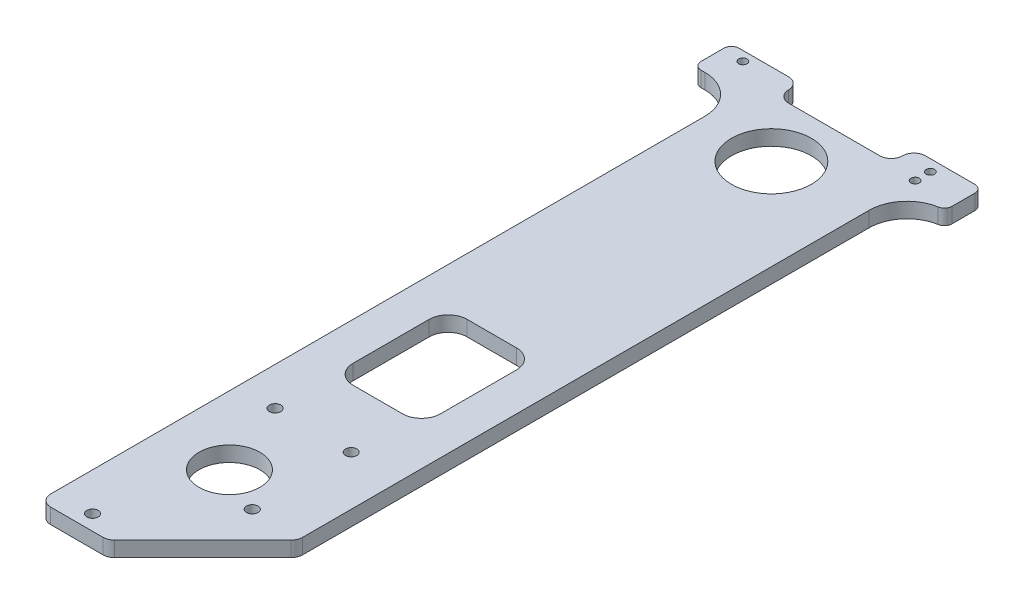
SolidWorks part; units mm, degrees
material "Thornel Mat VMA"
ref_plane "前视基准面" through (0, 0, 0) normal (0, 0, 1) x (1, 0, 0)
ref_plane "上视基准面" through (0, 0, 0) normal (0, 1, 0) x (1, 0, 0)
ref_plane "右视基准面" through (0, 0, 0) normal (1, 0, 0) x (0, 0, -1)
other "Configuration Table"
sketch "草图1" plane through (0, 0, 0) normal (0, 1, 0) x (1, 0, 0)
  line L0 (0, 0) -> (70.3815, 0) construction
  line L1 (-33, -97.5) -> (33, -97.5)
  line L2 (-33, -97.5) -> (-33, 97.5)
  line L3 (-33, 97.5) -> (33, 97.5)
  line L4 (33, -97.5) -> (33, 97.5)
  line L5 (-33, -97.5) -> (33, 97.5) construction
  line L6 (-33, 97.5) -> (33, -97.5) construction
  line L7 (0, -45.5) -> (63.9677, -45.5) construction
  line L8 (0, 0) -> (0, -67.9018) construction
  line L9 (0, 0) -> (0, 59.2148) construction
  line L14 (-20, -97.5) -> (-20, 87.5)
  line L15 (-20, 87.5) -> (-33, 87.5)
  line L16 (0, 92.5) -> (68.8821, 92.5) construction
  line L17 (-1.5, 44.6746) -> (-1.5, 61.6414) construction
  line L19 (-31, 88) -> (31, 88) construction
  line L20 (-31, 88) -> (-31, 97) construction
  line L21 (-31, 97) -> (31, 97) construction
  line L22 (31, 88) -> (31, 97) construction
  line L23 (-31, 88) -> (31, 97) construction
  line L24 (-31, 97) -> (31, 88) construction
  line L29 (23, -97.5243) -> (23, 87.5)
  line L30 (23, 87.5) -> (33, 87.5)
  line L37 (-10, -45.5) -> (-10, -112.6313) construction
  line L49 (10, -45.5) -> (10, -85.1506) construction
  line L50 (10, 0) -> (13, 0)
  line L55 (-10, -30) -> (10, -30)
  line L56 (-10, -30) -> (-10, 0)
  line L57 (-10, 0) -> (10, 0)
  line L58 (10, -30) -> (10, 0)
  line L59 (-10, -30) -> (10, 0) construction
  line L60 (-10, 0) -> (10, -30) construction
  line L61 (13, 0) -> (13, -30)
  line L62 (13, -30) -> (10, -30)
  line L63 (-1, 80.0182) -> (-1, 48.3003) construction
  line L66 (1.5, 44.6746) -> (1.5, 61.6414) construction
  line L68 (-33, 17.5) -> (-20, 17.5)
  line L69 (33, 17.5) -> (23, 17.5)
  circle A0 centre (10, -45.5) radius 1.5
  circle A1 centre (-10, -45.5) radius 1.5
  circle A2 centre (22.3, 94.5) radius 1.1
  circle A3 centre (22.3, 90.5) radius 1.1
  circle A4 centre (-27.5, 95) radius 1.1
  circle A6 centre (-10, -93.5) radius 1.5
  circle A7 centre (10, -71.5) radius 1.5
  circle A8 centre (-2, -65.5) radius 8
  circle A9 centre (-1, 76) radius 10.5
  point P0 (0, 0)
  point P34 (0, -15)
  dimension "D4" = 3
  dimension "D5" = 20
  dimension "D10" = 2.2
  dimension "D11" = 4
  dimension "D14" = 8.7
  dimension "D15" = 2.2
  dimension "D16" = 2
  dimension "D17" = 3.5
  dimension "D21" = 30
  dimension "D18" = 3
  dimension "D20" = 3
  dimension "D23" = 48
  dimension "D24" = 26
  dimension "D27" = 16
  dimension "D28" = 2
  dimension "D29" = 20
  dimension "D30" = 1
  dimension "D31" = 21
  dimension "D32" = 76
  dimension "D1" = 66
  dimension "D2" = 195
  dimension "D3" = 52
  dimension "D6" = 185
  dimension "D7" = 13
  dimension "D8" = 138
  dimension "D9" = 1.5
  dimension "D12" = 62
  dimension "D13" = 9
  dimension "D19" = 20
  dimension "D22" = 15
  dimension "D25" = 10
  dimension "D26" = 3
  dimension "D33" = 70
extrude "凸台-拉伸1" add sketch "草图1" along normal blind 4 contours L29 L30 L4 L3 L2 L15 L14 L1 A9 A8 A7 A6 A4 A1 A0 L61 L62 L55 L56 L57 L50 A2 A3 region at (1.5782, 0, -2.6188)
sketch "草图3" plane through (0, 4, 0) normal (0, 1, 0) x (1, 0, 0)
  line L0 (0, 0) -> (0, 63.5643) construction
  line L1 (-15, 97.5) -> (-15, 91.5)
  line L2 (-33, 97.5) -> (33, 97.5) construction
  line L3 (-15, 91.5) -> (15, 91.5)
  line L4 (-15, 97.5) -> (15, 97.5)
  line L5 (15, 97.5) -> (15, 91.5)
  point P10 (0, 97.5)
  point P11 (0, 91.5)
  dimension "D1" = 6
  dimension "D2" = 30
extrude "切除-拉伸1" cut sketch "草图3" against normal blind 5
fillet "圆角4" radius 3 4 edges at (15, 2, -97.5) (15, 2, -91.5) (-15, 2, -91.5) (-15, 2, -97.5)
chamfer "倒角1" distance 25 angle 45 1 edges at (23, 2, 97.5)
fillet "圆角8" radius 5 4 edges at (-10, 2, 30) (-10, 2, 0) (13, 2, 30) (13, 2, 0)
sketch "草图5" plane through (0, 4, 0) normal (0, 1, 0) x (1, 0, 0)
  line L0 (-33, -57.5) -> (-20, -57.5)
  line L1 (-33, 87.5) -> (-33, 97.5) construction
  line L2 (-20, -57.5) -> (-20, -97.5)
  line L4 (-20, -97.5) -> (-33, -97.5)
  line L5 (-33, -97.5) -> (-33, -57.5)
  line L6 (-20, -97.5) -> (-2, -97.5) construction
  dimension "D1" = 40
  dimension "D2" = 13
fillet "圆角12" radius 2 4 edges at (-33, 2, -97.5) (-33, 2, -87.5) (33, 2, -97.5) (33, 2, -87.5)
fillet "圆角13" radius 3 3 edges at (23, 2, 72.5) (-2, 2, 97.5) (-20, 2, 97.5)
fillet "圆角14" radius 10 2 edges at (23, 2, -87.5) (-20, 2, -87.5)
